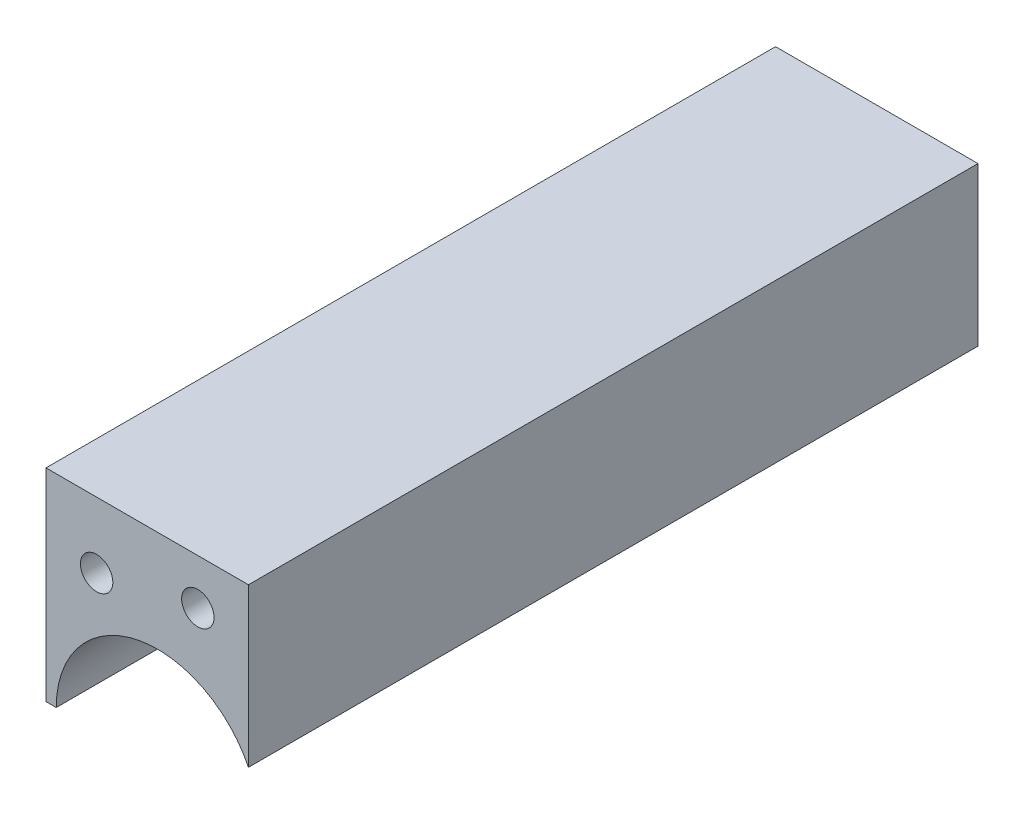
SolidWorks part; units mm, degrees
ref_plane "Front Plane" through (0, 0, 0) normal (0, 0, 1) x (1, 0, 0)
ref_plane "Top Plane" through (0, 0, 0) normal (0, 1, 0) x (1, 0, 0)
ref_plane "Right Plane" through (0, 0, 0) normal (1, 0, 0) x (0, 0, -1)
sketch "Sketch1" plane through (0, 0, 0) normal (0, 0, 1) x (1, 0, 0)
  line L1 (0, 0) -> (1.01, 0)
  line L2 (0, 0) -> (0, 20)
  line L3 (0, 20) -> (20, 20)
  line L4 (20, 4.3795) -> (20, 20)
  arc A0 (20, 4.3795) -> (1.01, 0) centre (11.01, 0) ccw
  circle A1 centre (5, 13.5) radius 1.6
  circle A2 centre (15, 15.5) radius 1.6
  point P9 (-25.9562, 13.9053)
  point P10 (-27.5515, 1.0292)
  point P11 (51.6918, 12.0242)
  point P12 (-29.0217, -1.5254)
extrude "Boss-Extrude2" add sketch "Sketch1" along normal blind 72.07
